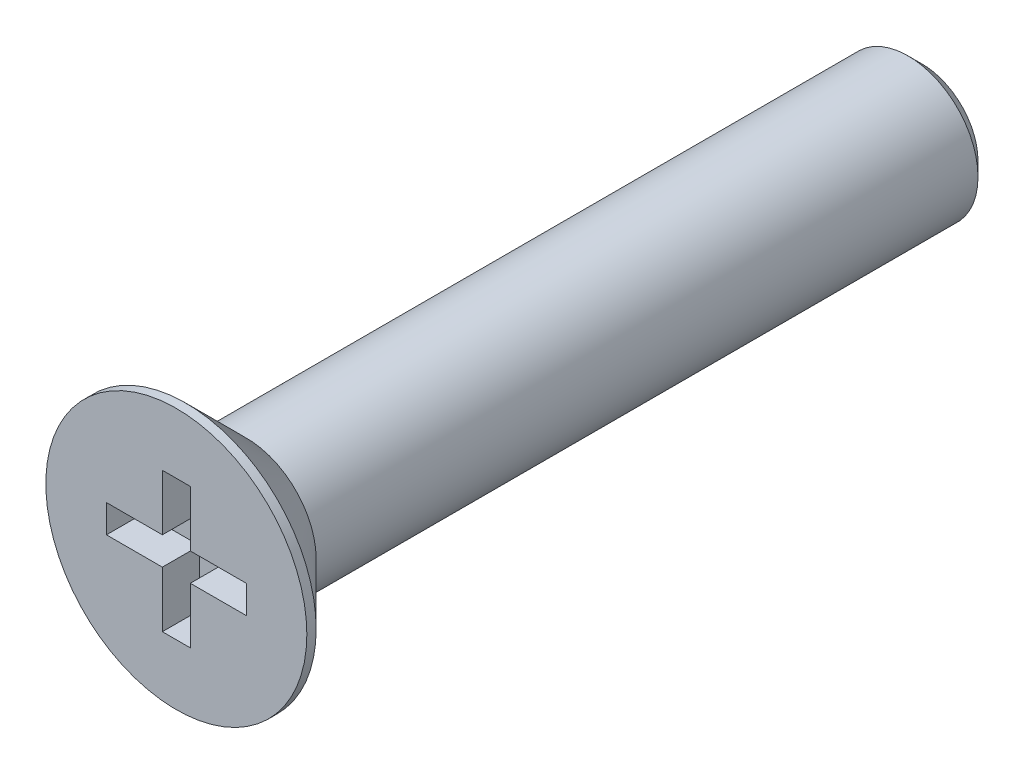
SolidWorks part; units mm, degrees
ref_plane "Ebene vorne" through (0, 0, 0) normal (0, 0, 1) x (1, 0, 0)
ref_plane "Ebene oben" through (0, 0, 0) normal (0, 1, 0) x (1, 0, 0)
ref_plane "Ebene rechts" through (0, 0, 0) normal (1, 0, 0) x (0, 0, -1)
sketch "Skizze1" plane through (0, 0, 0) normal (1, 0, 0) x (0, 0, -1)
  line L0 (-31.7636, 0) -> (42.9935, 0) construction
  line L1 (0, 26.0256) -> (0, -29.3045) construction
  line L2 (0, 0) -> (0, 2.8)
  line L3 (0.2, 2.8) -> (1.5, 1.5)
  line L4 (1.5, 1.5) -> (16, 1.5)
  line L5 (16, 1.5) -> (16, 0)
  line L6 (16, 0) -> (0, 0)
  line L7 (0, 2.8) -> (0.2, 2.8)
  dimension "D1" = 3
  dimension "D2" = 16
  dimension "D3" = 5.6
  dimension "D4" = 45
  dimension "D5" = 1.5
  dimension "D6" = 0.2
revolve "Rotation1" add sketch "Skizze1" angle 360 about L0
sketch "Skizze3" plane through (0, 0, 0) normal (0, 0, 1) x (1, 0, 0)
  line L0 (0, 1.5356) -> (0, -1.3958) construction
  line L1 (-1.5297, 0) -> (1.3792, 0) construction
  line L2 (-1.5, -0.3) -> (-1.5, 0.3)
  line L3 (-1.5, 0.3) -> (-0.3, 0.3)
  line L4 (-0.3, 0.3) -> (-0.3, 1.5)
  line L5 (-0.3, 1.5) -> (0.3, 1.5)
  line L6 (0.3, 0.3) -> (0.3, 1.5)
  line L7 (1.5, 0.3) -> (0.3, 0.3)
  line L8 (1.5, -0.3) -> (1.5, 0.3)
  line L9 (1.5, -0.3) -> (0.3, -0.3)
  line L10 (0.3, -0.3) -> (0.3, -1.5)
  line L11 (-0.3, -1.5) -> (0.3, -1.5)
  line L12 (-0.3, -0.3) -> (-0.3, -1.5)
  line L13 (-1.5, -0.3) -> (-0.3, -0.3)
  point P11 (0, 1.5)
  point P14 (0, -1.5)
  point P16 (1.5, 0)
  point P21 (-1.5, 0)
  dimension "D1" = 0.6
  dimension "D2" = 3
extrude "Schnitt-Linear austragen1" cut sketch "Skizze3" against normal blind 0.8
chamfer "Fase1" distance 0.3 angle 45 1 edges at (1.5, 0, -16)
ref_axis "Achse1" through (0, 0, 0.8) along (0, 0, -1)
